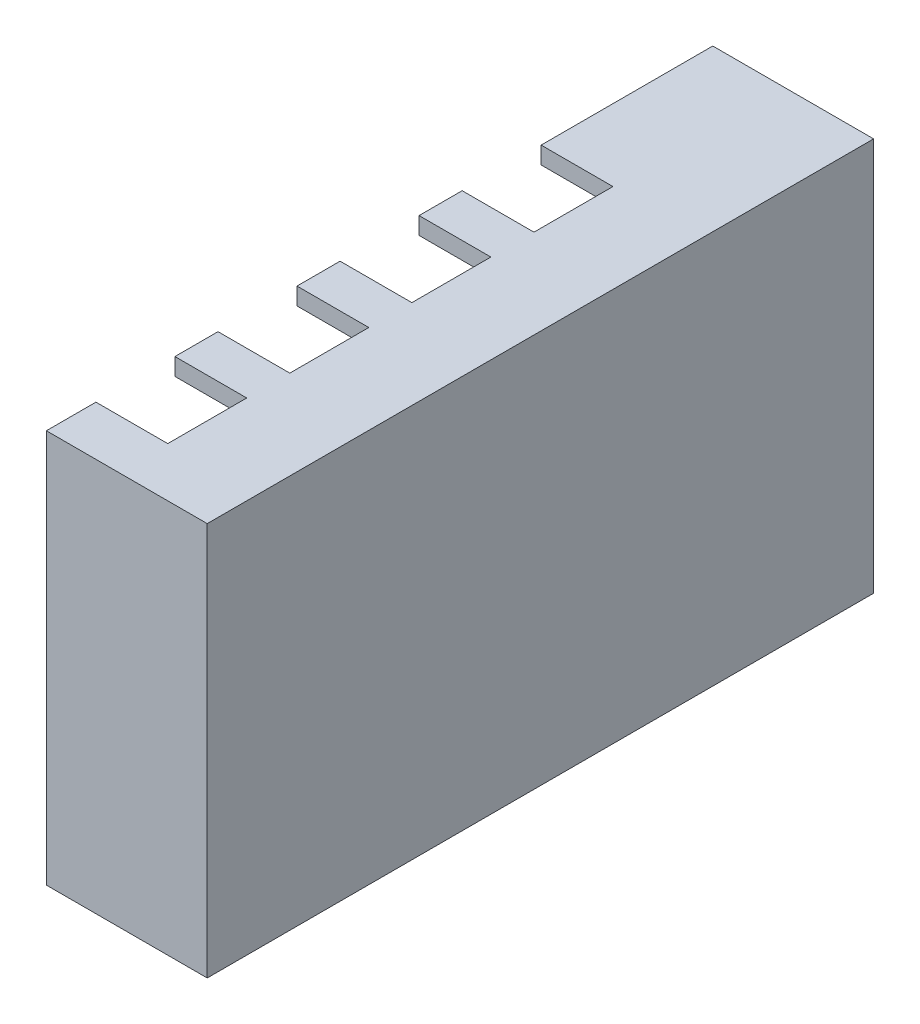
SolidWorks part; units mm, degrees
ref_plane "Front Plane" through (0, 0, 0) normal (0, 0, 1) x (1, 0, 0)
ref_plane "Top Plane" through (0, 0, 0) normal (0, 1, 0) x (1, 0, 0)
ref_plane "Right Plane" through (0, 0, 0) normal (1, 0, 0) x (0, 0, -1)
sketch "Sketch1" plane through (0, 0, 0) normal (1, 0, 0) x (0, 0, -1)
  line L1 (-22, -12.5) -> (22, -12.5)
  line L2 (-22, -12.5) -> (-22, 12.5)
  line L3 (-22, 12.5) -> (22, 12.5)
  line L4 (22, -12.5) -> (22, 12.5)
  line L5 (-22, -12.5) -> (22, 12.5) construction
  line L6 (-22, 12.5) -> (22, -12.5) construction
  point P0 (0, 0)
  dimension "D1" = 44
  dimension "D2" = 25
extrude "Boss-Extrude1" add sketch "Sketch1" along normal blind 10
shell "Shell2" thickness 1.2 removed face at (0, 0, 0) outward yes
sketch "Sketch2" plane through (0, 12.5, 0) normal (0, -1, 0) x (1, 0, 0)
  line L0 (0, 19.75) -> (0, 14.25)
  line L1 (0, 19.75) -> (5, 19.75)
  line L2 (0, 14.25) -> (5, 14.25)
  line L3 (5, 19.75) -> (5, 14.25)
  line L4 (0, -22) -> (0, 22) construction
  line L5 (0, 11.25) -> (0, 5.75)
  line L6 (0, 11.25) -> (5, 11.25)
  line L7 (0, 5.75) -> (5, 5.75)
  line L8 (5, 11.25) -> (5, 5.75)
  line L10 (0, -23.2) -> (0, 23.2) construction
  line L11 (0, 2.75) -> (5, 2.75)
  line L12 (0, 2.75) -> (0, -2.75)
  line L13 (5, 2.75) -> (5, -2.75)
  line L14 (0, -2.75) -> (5, -2.75)
  line L15 (0, -5.75) -> (5, -5.75)
  line L16 (0, -5.75) -> (0, -11.25)
  line L17 (5, -5.75) -> (5, -11.25)
  line L18 (0, -11.25) -> (5, -11.25)
  point P13 (0, 0)
  point P14 (0, 0)
  dimension "D1" = 2.25
  dimension "D2" = 5.5
  dimension "D3" = 5
  dimension "D4" = 3
  dimension "D5" = 5.5
  dimension "D6" = 3
  dimension "D7" = 5.5
  dimension "D8" = 5.5
  dimension "D9" = 3
extrude "Cut-Extrude1" cut sketch "Sketch2" against normal up to surface (1.2 mm away) up to face at (5.6, 13.7, 0)
sketch "Sketch3" plane through (0, 0, -23.2) normal (0, 0, -1) x (-1, 0, 0)
  line L0 (0, -13.7) -> (0, 13.7) construction
  line L1 (0, 0.5) -> (-1.95, 0.5)
  line L2 (0, 0.5) -> (0, -4)
  line L3 (0, -4) -> (-1.95, -4)
  line L4 (-10, 12.5) -> (0, 12.5) construction
  line L5 (-10, 12.5) -> (0, 12.5) construction
  line L7 (0, 9.5) -> (-4.2, 9.5)
  line L8 (0, 9.5) -> (0, 4.5)
  line L9 (0, 4.5) -> (-4.2, 4.5)
  line L10 (-4.2, 9.5) -> (-4.2, 4.5)
  arc A0 (-1.95, -4) -> (-1.95, 0.5) centre (-1.95, -1.75) cw
  point P7 (-4.2, -1.75)
  dimension "D1" = 4.2
  dimension "D2" = 4.5
  dimension "D3" = 12
  dimension "D4" = 4.2
  dimension "D5" = 5
  dimension "D6" = 3
extrude "Cut-Extrude2" cut sketch "Sketch3" against normal up to surface (1.2 mm away) up to face at (5, 0, -22)
